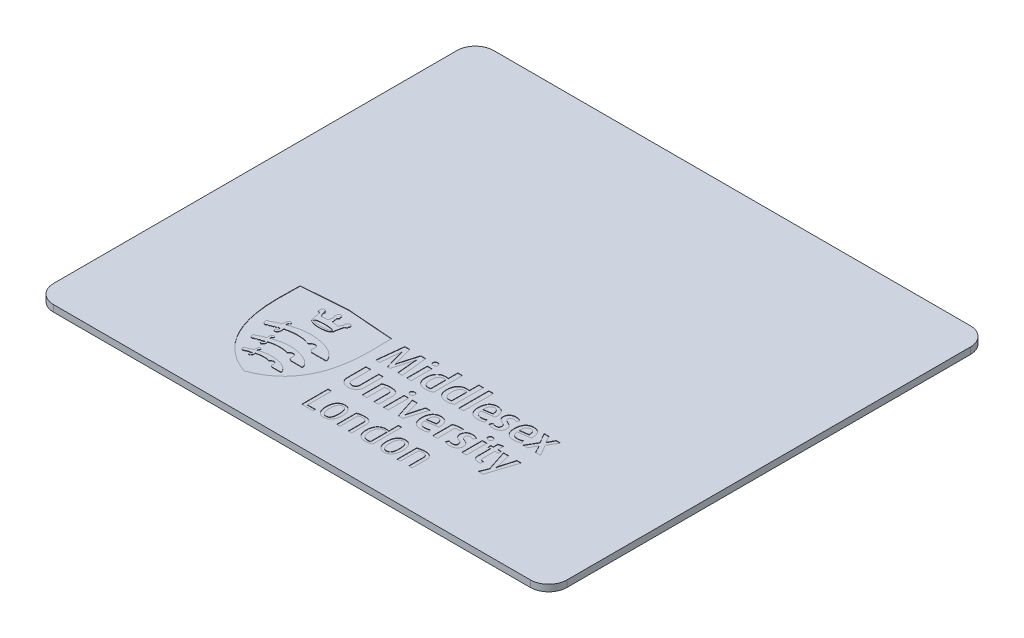
SolidWorks part; units mm, degrees
material "ABS"
ref_plane "Front Plane" through (0, 0, 0) normal (0, 0, 1) x (1, 0, 0)
ref_plane "Top Plane" through (0, 0, 0) normal (0, 1, 0) x (1, 0, 0)
ref_plane "Right Plane" through (0, 0, 0) normal (1, 0, 0) x (0, 0, -1)
sketch "Sketch1" plane through (0, 0, 0) normal (0, 1, 0) x (1, 0, 0)
  line L1 (-700, 600) -> (700, 600)
  line L2 (-700, 600) -> (-700, -600)
  line L3 (-700, -600) -> (700, -600)
  line L4 (700, 600) -> (700, -600)
  line L5 (0, -600) -> (0, 600) construction
  line L6 (-700, 0) -> (700, 0) construction
  point P0 (0, 0)
  dimension "D1" = 1400
  dimension "D2" = 1200
extrude "Boss-Extrude1" add sketch "Sketch1" along normal blind 18
sketch "Sketch2" plane through (0, 0, 0) normal (0, -1, 0) x (1, 0, 0)
  circle A0 centre (0, 0) radius 5
extrude "Cut-Extrude1" cut sketch "Sketch2" against normal blind 1
fillet "Fillet1" radius 50 4 edges at (700, 9, -600) (700, 9, 600) (-700, 9, 600) (-700, 9, -600)
sketch "Sketch3" plane through (0, 18, 0) normal (0, 1, 0) x (1, 0, 0)
  line L0 (-108.937, -219.6886) -> (-234.7326, -210.062)
  line L1 (-234.7326, -210.062) -> (-358.2136, -219.2576)
  line L2 (-24.6354, -235.7994) -> (-24.8453, -235.7994)
  line L3 (-40.5789, -291.8555) -> (-48.0791, -291.8555)
  line L4 (-63.7066, -235.7994) -> (-63.9144, -235.7994)
  line L5 (-68.808, -291.8555) -> (-79.9628, -291.8555)
  line L6 (-79.9628, -291.8555) -> (-71.9409, -220.1722)
  line L7 (-71.9409, -220.1722) -> (-58.6049, -220.1722)
  line L8 (-58.6049, -220.1722) -> (-45.7821, -266.1213)
  line L9 (-43.9096, -274.1443) -> (-43.7005, -274.1443)
  line L10 (-41.8247, -266.1213) -> (-28.5982, -220.1722)
  line L11 (-28.5982, -220.1722) -> (-15.2571, -220.1722)
  line L12 (-15.2571, -220.1722) -> (-7.2304, -291.8555)
  line L13 (-7.2304, -291.8555) -> (-19.7405, -291.8555)
  line L14 (4.7523, -235.6977) -> (17.4635, -235.6977)
  line L15 (17.4635, -235.6977) -> (17.4635, -291.8555)
  line L16 (17.4635, -291.8555) -> (4.7523, -291.8555)
  line L17 (4.7523, -291.8555) -> (4.7523, -235.6977)
  line L18 (62.3691, -283.5184) -> (62.3691, -243.0942)
  line L19 (62.3691, -236.2174) -> (62.3691, -210.0652)
  line L20 (62.3691, -210.0652) -> (75.0815, -210.0652)
  line L21 (75.0815, -210.0652) -> (75.0815, -288.8365)
  line L22 (119.5758, -283.5184) -> (119.5758, -243.0942)
  line L23 (119.5758, -236.2174) -> (119.5758, -210.0652)
  line L24 (119.5758, -210.0652) -> (132.2904, -210.0652)
  line L25 (132.2904, -210.0652) -> (132.2904, -288.8365)
  line L26 (146.9693, -210.0652) -> (159.6729, -210.0652)
  line L27 (159.6729, -210.0652) -> (159.6729, -291.8555)
  line L28 (159.6729, -291.8555) -> (146.9693, -291.8555)
  line L29 (146.9693, -291.8555) -> (146.9693, -210.0652)
  line L30 (183.0194, -261.9537) -> (206.2499, -258.4109)
  line L31 (213.2263, -280.9174) -> (216.2497, -288.9393)
  line L32 (218.1244, -263.4141) -> (183.7434, -268.415)
  line L33 (225.9145, -288.7294) -> (229.2617, -280.6033)
  line L34 (259.7856, -238.6117) -> (256.664, -246.0124)
  line L35 (281.883, -261.9537) -> (305.1112, -258.4109)
  line L36 (312.0987, -280.9174) -> (315.122, -288.9393)
  line L37 (316.988, -263.4141) -> (282.618, -268.415)
  line L38 (356.0547, -291.8555) -> (345.5278, -271.4349)
  line L39 (345.5278, -271.4349) -> (345.3244, -271.4349)
  line L40 (345.3244, -271.4349) -> (334.5832, -291.8555)
  line L41 (334.5832, -291.8555) -> (321.6674, -291.8555)
  line L42 (321.6674, -291.8555) -> (339.0722, -262.7895)
  line L43 (339.0722, -262.7895) -> (323.4394, -235.6977)
  line L44 (323.4394, -235.6977) -> (336.7839, -235.6977)
  line L45 (336.7839, -235.6977) -> (346.2608, -254.0335)
  line L46 (346.2608, -254.0335) -> (346.4664, -254.0335)
  line L47 (346.4664, -254.0335) -> (356.3632, -235.6977)
  line L48 (356.3632, -235.6977) -> (368.3383, -235.6977)
  line L49 (368.3383, -235.6977) -> (352.408, -261.9548)
  line L50 (352.408, -261.9548) -> (370.0119, -291.8555)
  line L51 (370.0119, -291.8555) -> (356.0547, -291.8555)
  line L52 (-77.3618, -371.7369) -> (-77.3618, -320.8951)
  line L53 (-77.3618, -320.8951) -> (-64.1232, -320.8951)
  line L54 (-64.1232, -320.8951) -> (-64.1232, -371.6363)
  line L55 (-42.3444, -371.6363) -> (-42.3444, -320.8951)
  line L56 (-42.3444, -320.8951) -> (-30.0518, -320.8951)
  line L57 (-30.0518, -320.8951) -> (-30.0518, -371.7369)
  line L58 (15.6893, -392.5764) -> (15.6893, -352.779)
  line L59 (-3.1681, -344.9679) -> (-3.1681, -392.5764)
  line L60 (-3.1681, -392.5764) -> (-15.8805, -392.5764)
  line L61 (-15.8805, -392.5764) -> (-15.8805, -339.4419)
  line L62 (28.4039, -352.5689) -> (28.4039, -392.5764)
  line L63 (28.4039, -392.5764) -> (15.6893, -392.5764)
  line L64 (42.3654, -336.4166) -> (55.0734, -336.4166)
  line L65 (55.0734, -336.4166) -> (55.0734, -392.572)
  line L66 (55.0734, -392.572) -> (42.3654, -392.572)
  line L67 (42.3654, -392.572) -> (42.3654, -336.4166)
  line L68 (94.8796, -392.5764) -> (82.7907, -392.5764)
  line L69 (82.7907, -392.5764) -> (64.454, -336.4197)
  line L70 (64.454, -336.4197) -> (77.9997, -336.4197)
  line L71 (77.9997, -336.4197) -> (87.8921, -372.6798)
  line L72 (89.253, -380.387) -> (89.4587, -380.387)
  line L73 (90.9199, -372.6798) -> (101.0203, -336.4197)
  line L74 (101.0203, -336.4197) -> (112.9013, -336.4197)
  line L75 (112.9013, -336.4197) -> (94.8796, -392.5764)
  line L76 (129.6629, -362.678) -> (152.8956, -359.1361)
  line L77 (159.8743, -381.6448) -> (162.9019, -389.6625)
  line L78 (164.7701, -364.1372) -> (130.3914, -369.1336)
  line L79 (189.0508, -345.1704) -> (189.0508, -392.5764)
  line L80 (189.0508, -392.5764) -> (176.3362, -392.5764)
  line L81 (176.3362, -392.5764) -> (176.3362, -339.441)
  line L82 (203.4345, -335.4791) -> (200.9273, -344.7569)
  line L83 (208.3216, -389.4568) -> (211.6511, -381.3276)
  line L84 (242.1817, -339.3391) -> (239.0643, -346.7378)
  line L85 (255.4214, -336.4166) -> (268.1337, -336.4166)
  line L86 (268.1337, -336.4166) -> (268.1337, -392.572)
  line L87 (268.1337, -392.572) -> (255.4214, -392.572)
  line L88 (255.4214, -392.572) -> (255.4214, -336.4166)
  line L89 (285.3221, -377.9893) -> (285.3221, -344.5467)
  line L90 (285.3221, -344.5467) -> (279.0784, -344.5467)
  line L91 (279.0784, -344.5467) -> (279.0784, -336.4166)
  line L92 (279.0784, -336.4166) -> (285.3221, -336.4166)
  line L93 (285.3221, -336.4166) -> (285.3221, -324.0181)
  line L94 (285.3221, -324.0181) -> (298.0432, -320.4785)
  line L95 (298.0432, -320.4785) -> (298.0432, -336.4166)
  line L96 (298.0432, -336.4166) -> (307.2026, -336.4166)
  line L97 (307.2026, -336.4166) -> (307.2026, -344.5467)
  line L98 (307.2026, -344.5467) -> (298.0432, -344.5467)
  line L99 (298.0432, -344.5467) -> (298.0432, -377.3679)
  line L100 (307.2026, -384.143) -> (307.2026, -392.0536)
  line L101 (336.0729, -414.9778) -> (322.63, -414.9778)
  line L102 (322.63, -414.9778) -> (331.796, -392.572)
  line L103 (331.796, -392.572) -> (313.2472, -336.4186)
  line L104 (313.2472, -336.4186) -> (326.8018, -336.4186)
  line L105 (326.8018, -336.4186) -> (336.4864, -372.7826)
  line L106 (337.6304, -380.809) -> (337.8406, -380.809)
  line L107 (339.3916, -372.7826) -> (349.8222, -336.4186)
  line L108 (349.8222, -336.4186) -> (361.7012, -336.4186)
  line L109 (361.7012, -336.4186) -> (336.0729, -414.9778)
  line L110 (-76.4178, -496.7756) -> (-76.4178, -425.0979)
  line L111 (-76.4178, -425.0979) -> (-66.8338, -425.0979)
  line L112 (-66.8338, -425.0979) -> (-66.8338, -490.3155)
  line L113 (-66.8338, -490.3155) -> (-45.2626, -490.3155)
  line L114 (-45.2626, -490.3155) -> (-45.2626, -496.7756)
  line L115 (-45.2626, -496.7756) -> (-76.4178, -496.7756)
  line L116 (50.2847, -496.7756) -> (50.2847, -456.4531)
  line L117 (27.8811, -447.497) -> (27.8811, -496.7756)
  line L118 (27.8811, -496.7756) -> (18.7149, -496.7756)
  line L119 (18.7149, -496.7756) -> (18.7149, -443.5286)
  line L120 (59.4574, -456.2497) -> (59.4574, -496.7756)
  line L121 (59.4574, -496.7756) -> (50.2847, -496.7756)
  line L122 (105.2927, -490.2149) -> (105.2927, -446.4491)
  line L123 (105.2927, -441.3431) -> (105.2927, -414.9821)
  line L124 (105.2927, -414.9821) -> (114.3605, -414.9821)
  line L125 (114.3605, -414.9821) -> (114.3605, -493.8661)
  line L126 (215.0113, -496.7756) -> (215.0113, -456.4531)
  line L127 (192.6099, -447.497) -> (192.6099, -496.7756)
  line L128 (192.6099, -496.7756) -> (183.4482, -496.7756)
  line L129 (183.4482, -496.7756) -> (183.4482, -443.5286)
  line L130 (224.1862, -456.2497) -> (224.1862, -496.7756)
  line L131 (224.1862, -496.7756) -> (215.0113, -496.7756)
  line L132 (-287.6033, -317.3665) -> (-287.8495, -317.476)
  line L133 (-283.8428, -360.4576) -> (-283.5695, -360.357)
  line L134 (-192.9487, -354.5454) -> (-186.1037, -360.9652)
  line L135 (-186.1037, -360.9652) -> (-145.5361, -360.9652)
  line L136 (-145.5361, -360.9652) -> (-145.5361, -360.2519)
  line L137 (-277.5347, -373.0626) -> (-277.7809, -373.1612)
  line L138 (-275.9499, -402.3069) -> (-275.9958, -402.3069)
  line L139 (-274.3748, -408.5417) -> (-274.1517, -408.4521)
  line L140 (-201.5593, -403.3986) -> (-195.3584, -408.8304)
  line L141 (-195.3584, -408.8304) -> (-162.7178, -408.8304)
  line L142 (-162.7178, -408.8304) -> (-162.7178, -408.1152)
  line L143 (-231.3232, -424.039) -> (-231.8711, -424.0345)
  line L144 (-264.1125, -430.4095) -> (-265.003, -430.72)
  line L145 (-266.9904, -420.6875) -> (-267.1687, -420.7664)
  line L146 (-264.2767, -450.8113) -> (-264.037, -450.715)
  line L147 (-210.0286, -445.6659) -> (-205.3461, -449.4549)
  line L148 (-205.3461, -449.4549) -> (-180.6346, -449.4549)
  line L149 (-180.6346, -449.4549) -> (-180.6346, -448.7417)
  line L150 (-204.3125, -247.2035) -> (-207.3172, -248.2963)
  line L151 (-207.3172, -248.2963) -> (-205.3165, -253.8025)
  line L152 (-230.9809, -246.1775) -> (-226.8288, -242.0398)
  line L153 (-226.8288, -242.0398) -> (-229.0962, -239.7799)
  line L154 (-239.3222, -239.7777) -> (-241.5767, -242.0342)
  line L155 (-241.5767, -242.0342) -> (-237.4244, -246.1896)
  line L156 (-262.6327, -253.7983) -> (-260.6331, -248.2963)
  line L157 (-260.6331, -248.2963) -> (-263.6412, -247.2035)
  line L158 (-272.9102, -251.5263) -> (-273.9951, -254.5279)
  line L159 (-273.9951, -254.5279) -> (-268.4474, -256.5492)
  line L160 (-199.528, -256.5579) -> (-193.9518, -254.5279)
  line L161 (-193.9518, -254.5279) -> (-195.0412, -251.5263)
  spline S0 degree 2 poles (-358.2136, -219.2576) (-359.0843, -246.2586) (-359.0843, -279.7218) knots 2 2 2 3 3 3
  spline S1 degree 2 poles (-359.0843, -279.7218) (-359.0843, -451.1395) (-233.9723, -496.7953) knots 3 3 3 4 4 4
  spline S2 degree 2 poles (-233.9723, -496.7953) (-108.0609, -451.5748) (-108.0609, -280.1549) knots 4 4 4 5 5 5
  spline S3 degree 2 poles (-108.0609, -280.1549) (-108.0609, -246.6939) (-108.937, -219.6886) knots 5 5 5 6 6 6
  spline S4 degree 2 poles (-19.7405, -291.8555) (-19.8402, -290.0867) (-24.3225, -244.4495) knots 0 0 0 1 1 1
  spline S5 degree 2 poles (-24.3225, -244.4495) (-24.7337, -239.9659) (-24.6354, -235.7994) knots 1 1 1 2 2 2
  spline S6 degree 2 poles (-24.8453, -235.7994) (-25.5716, -239.863) (-26.9226, -244.4495) knots 3 3 3 4 4 4
  spline S7 degree 2 poles (-26.9226, -244.4495) (-39.742, -289.4622) (-40.5789, -291.8555) knots 4 4 4 5 5 5
  spline S8 degree 2 poles (-48.0791, -291.8555) (-48.8043, -289.7729) (-61.6185, -244.3433) knots 6 6 6 7 7 7
  spline S9 degree 2 poles (-61.6185, -244.3433) (-62.8676, -239.863) (-63.7066, -235.7994) knots 7 7 7 8 8 8
  spline S10 degree 2 poles (-63.9144, -235.7994) (-63.8136, -239.863) (-64.226, -244.3433) knots 9 9 9 10 10 10
  spline S11 degree 2 poles (-64.226, -244.3433) (-68.7086, -289.7729) (-68.808, -291.8555) knots 10 10 10 11 11 11
  spline S12 degree 2 poles (-45.7821, -266.1213) (-44.5395, -270.7021) (-43.9096, -274.1443) knots 15 15 15 16 16 16
  spline S13 degree 2 poles (-43.7005, -274.1443) (-43.1788, -270.7021) (-41.8247, -266.1213) knots 17 17 17 18 18 18
  spline S14 degree 3 poles (11.1107, -213.4003) (15.0724, -213.4003) (18.0892, -216.2103) (18.0892, -219.7553) (18.0892, -223.1922) (15.0724, -226.0064) (11.1107, -226.0064) knots 2 2 2 2 3 3 3 4 4 4 4
  spline S15 degree 3 poles (11.1107, -226.0064) (7.2539, -226.0064) (4.1298, -223.1922) (4.1298, -219.7553) (4.1298, -216.2103) (7.2539, -213.4003) (11.1107, -213.4003) knots 0 0 0 0 1 1 1 2 2 2 2
  spline S16 degree 3 poles (62.3691, -243.0942) (60.5992, -242.5725) (58.7267, -242.3657) (56.7446, -242.3657) knots 0 0 0 0 1 1 1 1
  spline S17 degree 3 poles (56.7446, -242.3657) (45.6949, -242.3657) (41.9453, -251.8458) (41.9453, -263.7268) knots 1 1 1 1 2 2 2 2
  spline S18 degree 3 poles (41.9453, -263.7268) (41.9453, -276.4371) (46.0166, -284.772) (55.8127, -284.772) knots 2 2 2 2 3 3 3 3
  spline S19 degree 3 poles (55.8127, -284.772) (58.823, -284.772) (60.9144, -284.4602) (62.3691, -283.5184) knots 3 3 3 3 4 4 4 4
  spline S20 degree 3 poles (55.4935, -292.899) (38.9243, -292.899) (29.3423, -282.2713) (29.3423, -264.4542) knots 0 0 0 0 1 1 1 1
  spline S21 degree 3 poles (29.3423, -264.4542) (29.3423, -246.1175) (39.3443, -235.1749) (53.9357, -235.1749) knots 1 1 1 1 2 2 2 2
  spline S22 degree 3 poles (53.9357, -235.1749) (57.064, -235.1749) (59.8729, -235.4898) (62.3691, -236.2174) knots 2 2 2 2 3 3 3 3
  spline S23 degree 3 poles (75.0815, -288.8365) (70.6012, -291.3381) (64.2439, -292.899) (55.4935, -292.899) knots 6 6 6 6 7 7 7 7
  spline S24 degree 3 poles (119.5758, -243.0942) (117.8081, -242.5725) (115.9158, -242.3657) (113.947, -242.3657) knots 0 0 0 0 1 1 1 1
  spline S25 degree 3 poles (113.947, -242.3657) (102.9038, -242.3657) (99.1542, -251.8458) (99.1542, -263.7268) knots 1 1 1 1 2 2 2 2
  spline S26 degree 3 poles (99.1542, -263.7268) (99.1542, -276.4371) (103.208, -284.772) (113.0063, -284.772) knots 2 2 2 2 3 3 3 3
  spline S27 degree 3 poles (113.0063, -284.772) (116.0339, -284.772) (118.1078, -284.4602) (119.5758, -283.5184) knots 3 3 3 3 4 4 4 4
  spline S28 degree 3 poles (112.7044, -292.899) (96.1309, -292.899) (86.5447, -282.2713) (86.5447, -264.4542) knots 0 0 0 0 1 1 1 1
  spline S29 degree 3 poles (86.5447, -264.4542) (86.5447, -246.1175) (96.5465, -235.1749) (111.1316, -235.1749) knots 1 1 1 1 2 2 2 2
  spline S30 degree 3 poles (111.1316, -235.1749) (114.2577, -235.1749) (117.0753, -235.4898) (119.5758, -236.2174) knots 2 2 2 2 3 3 3 3
  spline S31 degree 3 poles (132.2904, -288.8365) (127.8078, -291.3381) (121.4528, -292.899) (112.7044, -292.899) knots 6 6 6 6 7 7 7 7
  spline S32 degree 3 poles (195.2002, -242.4663) (187.8104, -242.4663) (182.7045, -248.5129) (183.0194, -261.9537) knots 0 0 0 0 1 1 1 1
  spline S33 degree 3 poles (206.2499, -258.4109) (206.2499, -247.0548) (202.1831, -242.4663) (195.2002, -242.4663) knots 2 2 2 2 3 3 3 3
  spline S34 degree 3 poles (183.7434, -268.415) (184.7782, -278.8336) (189.7835, -284.039) (199.0548, -284.039) knots 0 0 0 0 1 1 1 1
  spline S35 degree 3 poles (199.0548, -284.039) (205.5172, -284.039) (210.2096, -282.4803) (213.2263, -280.9174) knots 1 1 1 1 2 2 2 2
  spline S36 degree 3 poles (216.2497, -288.9393) (212.29, -291.1271) (206.2499, -292.899) (197.7029, -292.899) knots 3 3 3 3 4 4 4 4
  spline S37 degree 3 poles (197.7029, -292.899) (181.7636, -292.899) (171.6525, -282.5843) (171.6525, -263.6208) knots 4 4 4 4 5 5 5 5
  spline S38 degree 3 poles (171.6525, -263.6208) (171.6525, -245.2828) (180.9303, -234.6531) (195.6312, -234.6531) knots 5 5 5 5 6 6 6 6
  spline S39 degree 3 poles (195.6312, -234.6531) (210.518, -234.6531) (218.6428, -244.5532) (218.1244, -263.4141) knots 6 6 6 6 7 7 7 7
  spline S40 degree 3 poles (241.4467, -292.7951) (234.8818, -292.7951) (229.2617, -291.0242) (225.9145, -288.7294) knots 0 0 0 0 1 1 1 1
  spline S41 degree 3 poles (229.2617, -280.6033) (231.3444, -282.2713) (235.1968, -283.8356) (239.7821, -283.8356) knots 2 2 2 2 3 3 3 3
  spline S42 degree 3 poles (239.7821, -283.8356) (244.9864, -283.8356) (248.4209, -280.4983) (248.4209, -275.9131) knots 3 3 3 3 4 4 4 4
  spline S43 degree 3 poles (248.4209, -275.9131) (248.4209, -271.121) (245.9227, -268.8296) (240.1911, -266.6441) knots 4 4 4 4 5 5 5 5
  spline S44 degree 3 poles (240.1911, -266.6441) (229.5679, -262.5794) (227.3825, -256.7472) (227.3825, -250.9105) knots 5 5 5 5 6 6 6 6
  spline S45 degree 3 poles (227.3825, -250.9105) (227.3825, -241.9479) (234.4595, -234.6531) (245.1963, -234.6531) knots 6 6 6 6 7 7 7 7
  spline S46 degree 3 poles (245.1963, -234.6531) (251.4442, -234.6531) (256.1259, -236.2174) (259.7856, -238.6117) knots 7 7 7 7 8 8 8 8
  spline S47 degree 3 poles (256.664, -246.0124) (254.9969, -244.6551) (251.6586, -242.8863) (247.699, -242.8863) knots 9 9 9 9 10 10 10 10
  spline S48 degree 3 poles (247.699, -242.8863) (242.4837, -242.8863) (239.6748, -246.3263) (239.6748, -250.2817) knots 10 10 10 10 11 11 11 11
  spline S49 degree 3 poles (239.6748, -250.2817) (239.6748, -254.8668) (243.1138, -257.1574) (248.0074, -259.1394) knots 11 11 11 11 12 12 12 12
  spline S50 degree 3 poles (248.0074, -259.1394) (258.9523, -263.5169) (261.4505, -269.1446) (261.4505, -275.7041) knots 12 12 12 12 13 13 13 13
  spline S51 degree 3 poles (261.4505, -275.7041) (261.4505, -284.8757) (253.7368, -292.7951) (241.4467, -292.7951) knots 13 13 13 13 14 14 14 14
  spline S52 degree 3 poles (294.0725, -242.4663) (286.6673, -242.4663) (281.5658, -248.5129) (281.883, -261.9537) knots 0 0 0 0 1 1 1 1
  spline S53 degree 3 poles (305.1112, -258.4109) (305.1112, -247.0548) (301.0532, -242.4663) (294.0725, -242.4663) knots 2 2 2 2 3 3 3 3
  spline S54 degree 3 poles (282.618, -268.415) (283.6572, -278.8336) (288.6559, -284.039) (297.9206, -284.039) knots 0 0 0 0 1 1 1 1
  spline S55 degree 3 poles (297.9206, -284.039) (304.3828, -284.039) (309.0709, -282.4803) (312.0987, -280.9174) knots 1 1 1 1 2 2 2 2
  spline S56 degree 3 poles (315.122, -288.9393) (311.1623, -291.1271) (305.1112, -292.899) (296.5707, -292.899) knots 3 3 3 3 4 4 4 4
  spline S57 degree 3 poles (296.5707, -292.899) (280.6317, -292.899) (270.5271, -282.5843) (270.5271, -263.6208) knots 4 4 4 4 5 5 5 5
  spline S58 degree 3 poles (270.5271, -263.6208) (270.5271, -245.2828) (279.7916, -234.6531) (294.4816, -234.6531) knots 5 5 5 5 6 6 6 6
  spline S59 degree 3 poles (294.4816, -234.6531) (309.3881, -234.6531) (317.5151, -244.5532) (316.988, -263.4141) knots 6 6 6 6 7 7 7 7
  spline S60 degree 3 poles (-53.7057, -393.725) (-67.769, -393.725) (-77.3618, -384.7599) (-77.3618, -371.7369) knots 0 0 0 0 1 1 1 1
  spline S61 degree 3 poles (-64.1232, -371.6363) (-64.1232, -379.3455) (-59.1158, -383.5108) (-53.1797, -383.5108) knots 4 4 4 4 5 5 5 5
  spline S62 degree 3 poles (-53.1797, -383.5108) (-47.1407, -383.5108) (-42.3444, -379.3455) (-42.3444, -371.6363) knots 5 5 5 5 6 6 6 6
  spline S63 degree 3 poles (-30.0518, -371.7369) (-30.0518, -384.7599) (-39.6372, -393.725) (-53.7057, -393.725) knots 9 9 9 9 10 10 10 10
  spline S64 degree 3 poles (15.6893, -352.779) (15.6893, -348.1948) (13.6024, -343.4027) (5.5868, -343.4027) knots 1 1 1 1 2 2 2 2
  spline S65 degree 3 poles (5.5868, -343.4027) (1.4161, -343.4027) (-0.7705, -344.023) (-3.1681, -344.9679) knots 2 2 2 2 3 3 3 3
  spline S66 degree 3 poles (-15.8805, -339.4419) (-10.5689, -336.9437) (-3.3792, -335.3839) (6.1065, -335.3839) knots 6 6 6 6 7 7 7 7
  spline S67 degree 3 poles (6.1065, -335.3839) (22.8802, -335.3839) (28.4039, -343.5044) (28.4039, -352.5689) knots 7 7 7 7 8 8 8 8
  spline S68 degree 3 poles (48.7227, -314.1212) (52.6888, -314.1212) (55.6989, -316.9377) (55.6989, -320.4785) (55.6989, -323.9187) (52.6888, -326.7307) (48.7227, -326.7307) knots 2 2 2 2 3 3 3 4 4 4 4
  spline S69 degree 3 poles (48.7227, -326.7307) (44.8723, -326.7307) (41.7374, -323.9187) (41.7374, -320.4785) (41.7374, -316.9377) (44.8723, -314.1212) (48.7227, -314.1212) knots 0 0 0 0 1 1 1 2 2 2 2
  spline S70 degree 2 poles (87.8921, -372.6798) (89.0451, -376.7445) (89.253, -380.387) knots 4 4 4 5 5 5
  spline S71 degree 2 poles (89.4587, -380.387) (89.7779, -376.8473) (90.9199, -372.6798) knots 6 6 6 7 7 7
  spline S72 degree 3 poles (141.8524, -343.1928) (134.4494, -343.1928) (129.3392, -349.236) (129.6629, -362.678) knots 0 0 0 0 1 1 1 1
  spline S73 degree 3 poles (152.8956, -359.1361) (152.8956, -347.7802) (148.8354, -343.1928) (141.8524, -343.1928) knots 2 2 2 2 3 3 3 3
  spline S74 degree 3 poles (130.3914, -369.1336) (131.4306, -379.5579) (136.4292, -384.7599) (145.6983, -384.7599) knots 0 0 0 0 1 1 1 1
  spline S75 degree 3 poles (145.6983, -384.7599) (152.1606, -384.7599) (156.8508, -383.2046) (159.8743, -381.6448) knots 1 1 1 1 2 2 2 2
  spline S76 degree 3 poles (162.9019, -389.6625) (158.9335, -391.8502) (152.8956, -393.6199) (144.3421, -393.6199) knots 3 3 3 3 4 4 4 4
  spline S77 degree 3 poles (144.3421, -393.6199) (128.4073, -393.6199) (118.3005, -383.3052) (118.3005, -364.3429) knots 4 4 4 4 5 5 5 5
  spline S78 degree 3 poles (118.3005, -364.3429) (118.3005, -346.0028) (127.5672, -335.3817) (142.2594, -335.3817) knots 5 5 5 5 6 6 6 6
  spline S79 degree 3 poles (142.2594, -335.3817) (157.1615, -335.3817) (165.2952, -345.2786) (164.7701, -364.1372) knots 6 6 6 6 7 7 7 7
  spline S80 degree 3 poles (200.9273, -344.7569) (196.6572, -343.301) (191.9712, -343.5044) (189.0508, -345.1704) knots 0 0 0 0 1 1 1 1
  spline S81 degree 3 poles (176.3362, -339.441) (182.1662, -336.6276) (189.2564, -335.0624) (203.4345, -335.4791) knots 4 4 4 4 5 5 5 5
  spline S82 degree 3 poles (223.8451, -393.5171) (217.2844, -393.5171) (211.6511, -391.7364) (208.3216, -389.4568) knots 0 0 0 0 1 1 1 1
  spline S83 degree 3 poles (211.6511, -381.3276) (213.7382, -382.999) (217.6016, -384.5565) (222.1824, -384.5565) knots 2 2 2 2 3 3 3 3
  spline S84 degree 3 poles (222.1824, -384.5565) (227.389, -384.5565) (230.8323, -381.2248) (230.8323, -376.6372) knots 3 3 3 3 4 4 4 4
  spline S85 degree 3 poles (230.8323, -376.6372) (230.8323, -371.8464) (228.3276, -369.5536) (222.6002, -367.3617) knots 4 4 4 4 5 5 5 5
  spline S86 degree 3 poles (222.6002, -367.3617) (211.9705, -363.3014) (209.783, -357.4726) (209.783, -351.6337) knots 5 5 5 5 6 6 6 6
  spline S87 degree 3 poles (209.783, -351.6337) (209.783, -342.6666) (216.8708, -335.3839) (227.6013, -335.3839) knots 6 6 6 6 7 7 7 7
  spline S88 degree 3 poles (227.6013, -335.3839) (233.8535, -335.3839) (238.5372, -336.9415) (242.1817, -339.3391) knots 7 7 7 7 8 8 8 8
  spline S89 degree 3 poles (239.0643, -346.7378) (237.4062, -345.3792) (234.0634, -343.6117) (230.0995, -343.6117) knots 9 9 9 9 10 10 10 10
  spline S90 degree 3 poles (230.0995, -343.6117) (224.8885, -343.6117) (222.0861, -347.0483) (222.0861, -351.0057) knots 10 10 10 10 11 11 11 11
  spline S91 degree 3 poles (222.0861, -351.0057) (222.0861, -355.5922) (225.5164, -357.8827) (230.4167, -359.8581) knots 11 11 11 11 12 12 12 12
  spline S92 degree 3 poles (230.4167, -359.8581) (241.3527, -364.242) (243.8531, -369.8731) (243.8531, -376.4315) knots 12 12 12 12 13 13 13 13
  spline S93 degree 3 poles (243.8531, -376.4315) (243.8531, -385.5977) (236.1418, -393.5171) (223.8451, -393.5171) knots 13 13 13 13 14 14 14 14
  spline S94 degree 3 poles (261.7829, -314.1212) (265.7361, -314.1212) (268.7616, -316.9377) (268.7616, -320.4785) (268.7616, -323.9187) (265.7361, -326.7307) (261.7829, -326.7307) knots 2 2 2 2 3 3 3 4 4 4 4
  spline S95 degree 3 poles (261.7829, -326.7307) (257.9241, -326.7307) (254.7957, -323.9187) (254.7957, -320.4785) (254.7957, -316.9377) (257.9241, -314.1212) (261.7829, -314.1212) knots 0 0 0 0 1 1 1 2 2 2 2
  spline S96 degree 3 poles (300.7492, -393.2021) (289.6973, -393.2021) (285.3221, -385.8079) (285.3221, -377.9893) knots 0 0 0 0 1 1 1 1
  spline S97 degree 3 poles (298.0432, -377.3679) (298.0432, -381.7476) (299.8086, -384.6593) (304.1838, -384.6593) knots 12 12 12 12 13 13 13 13
  spline S98 degree 3 poles (304.1838, -384.6593) (305.3301, -384.6593) (306.1679, -384.4515) (307.2026, -384.143) knots 13 13 13 13 14 14 14 14
  spline S99 degree 3 poles (307.2026, -392.0536) (306.0564, -392.5764) (303.7638, -393.2021) (300.7492, -393.2021) knots 15 15 15 15 16 16 16 16
  spline S100 degree 2 poles (336.4864, -372.7826) (337.6304, -377.1623) (337.6304, -380.809) knots 5 5 5 6 6 6
  spline S101 degree 2 poles (337.8406, -380.809) (338.1578, -377.1623) (339.3916, -372.7826) knots 7 7 7 8 8 8
  spline S102 degree 3 poles (-15.7765, -491.4663) (-5.0429, -491.4663) (-3.0676, -480.003) (-3.0676, -468.7477) (-3.0676, -457.4966) (-5.0429, -445.4079) (-15.7765, -445.4079) knots 2 2 2 2 3 3 3 4 4 4 4
  spline S103 degree 3 poles (-15.7765, -445.4079) (-26.5079, -445.4079) (-28.596, -457.3917) (-28.596, -468.7477) (-28.596, -480.1126) (-26.3056, -491.4663) (-15.7765, -491.4663) knots 0 0 0 0 1 1 1 2 2 2 2
  spline S104 degree 3 poles (-15.8805, -439.5777) (-0.4632, -439.5777) (6.1065, -451.9751) (6.1065, -468.7477) (6.1065, -485.214) (-0.566, -497.8258) (-15.7765, -497.8258) knots 2 2 2 2 3 3 3 4 4 4 4
  spline S105 degree 3 poles (-15.7765, -497.8258) (-31.0986, -497.8258) (-37.7633, -485.214) (-37.7633, -468.7477) (-37.7633, -451.9751) (-30.9871, -439.5777) (-15.8805, -439.5777) knots 0 0 0 0 1 1 1 2 2 2 2
  spline S106 degree 3 poles (50.2847, -456.4531) (50.2847, -451.2443) (48.0992, -445.515) (38.5085, -445.515) knots 1 1 1 1 2 2 2 2
  spline S107 degree 3 poles (38.5085, -445.515) (33.3065, -445.515) (30.8015, -446.2457) (27.8811, -447.497) knots 2 2 2 2 3 3 3 3
  spline S108 degree 3 poles (18.7149, -443.5286) (23.718, -441.1375) (30.2787, -439.5777) (39.2435, -439.5777) knots 6 6 6 6 7 7 7 7
  spline S109 degree 3 poles (39.2435, -439.5777) (54.8589, -439.5777) (59.4574, -448.2255) (59.4574, -456.2497) knots 7 7 7 7 8 8 8 8
  spline S110 degree 3 poles (105.2927, -446.4491) (103.0044, -445.8279) (100.7118, -445.4079) (98.3097, -445.4079) knots 0 0 0 0 1 1 1 1
  spline S111 degree 3 poles (98.3097, -445.4079) (85.2934, -445.4079) (81.1258, -456.6565) (81.1258, -468.8505) knots 1 1 1 1 2 2 2 2
  spline S112 degree 3 poles (81.1258, -468.8505) (81.1258, -482.0857) (85.7069, -491.7747) (97.1679, -491.7747) knots 2 2 2 2 3 3 3 3
  spline S113 degree 3 poles (97.1679, -491.7747) (100.9217, -491.7747) (103.5207, -491.3612) (105.2927, -490.2149) knots 3 3 3 3 4 4 4 4
  spline S114 degree 3 poles (96.7479, -497.8258) (80.7125, -497.8258) (72.0582, -486.5682) (72.0582, -469.5812) knots 0 0 0 0 1 1 1 1
  spline S115 degree 3 poles (72.0582, -469.5812) (72.0582, -450.9339) (81.9551, -440.0918) (96.4349, -440.0918) knots 1 1 1 1 2 2 2 2
  spline S116 degree 3 poles (96.4349, -440.0918) (99.5588, -440.0918) (102.2738, -440.5163) (105.2927, -441.3431) knots 2 2 2 2 3 3 3 3
  spline S117 degree 3 poles (114.3605, -493.8661) (110.6087, -496.1544) (104.5664, -497.8258) (96.7479, -497.8258) knots 6 6 6 6 7 7 7 7
  spline S118 degree 3 poles (148.9536, -491.4663) (159.6949, -491.4663) (161.6702, -480.003) (161.6702, -468.7477) (161.6702, -457.4966) (159.6949, -445.4079) (148.9536, -445.4079) knots 2 2 2 2 3 3 3 4 4 4 4
  spline S119 degree 3 poles (148.9536, -445.4079) (138.2296, -445.4079) (136.134, -457.3917) (136.134, -468.7477) (136.134, -480.1126) (138.4333, -491.4663) (148.9536, -491.4663) knots 0 0 0 0 1 1 1 2 2 2 2
  spline S120 degree 3 poles (148.8486, -439.5777) (164.267, -439.5777) (170.8387, -451.9751) (170.8387, -468.7477) (170.8387, -485.214) (164.1707, -497.8258) (148.9536, -497.8258) knots 2 2 2 2 3 3 3 4 4 4 4
  spline S121 degree 3 poles (148.9536, -497.8258) (133.6378, -497.8258) (126.9765, -485.214) (126.9765, -468.7477) (126.9765, -451.9751) (133.7494, -439.5777) (148.8486, -439.5777) knots 0 0 0 0 1 1 1 2 2 2 2
  spline S122 degree 3 poles (215.0113, -456.4531) (215.0113, -451.2443) (212.8281, -445.515) (203.2463, -445.515) knots 1 1 1 1 2 2 2 2
  spline S123 degree 3 poles (203.2463, -445.515) (198.031, -445.515) (195.5284, -446.2457) (192.6099, -447.497) knots 2 2 2 2 3 3 3 3
  spline S124 degree 3 poles (183.4482, -443.5286) (188.4491, -441.1375) (195.0033, -439.5777) (203.9681, -439.5777) knots 6 6 6 6 7 7 7 7
  spline S125 degree 3 poles (203.9681, -439.5777) (219.5966, -439.5777) (224.1862, -448.2255) (224.1862, -456.2497) knots 7 7 7 7 8 8 8 8
  spline S126 degree 3 poles (-229.5523, -319.5531) (-254.0144, -319.5531) (-276.1806, -327.4932) (-285.2594, -331.2363) knots 0 0 0 0 1 1 1 1
  spline S127 degree 3 poles (-285.2594, -331.2363) (-286.2547, -328.0893) (-285.9397, -326.0067) (-285.3885, -324.7159) knots 1 1 1 1 2 2 2 2
  spline S128 degree 3 poles (-285.3885, -324.7159) (-283.3013, -324.5398) (-281.653, -322.8544) (-281.653, -320.81) knots 2 2 2 2 3 3 3 3
  spline S129 degree 3 poles (-281.653, -320.81) (-281.653, -318.6496) (-283.4906, -316.8951) (-285.7516, -316.8951) knots 3 3 3 3 4 4 4 4
  spline S130 degree 3 poles (-285.7516, -316.8951) (-285.9516, -316.8951) (-286.1113, -316.9388) (-286.3159, -316.9935) knots 4 4 4 4 5 5 5 5
  spline S131 degree 3 poles (-286.3159, -316.9935) (-286.5435, -317.0188) (-286.7502, -317.0602) (-286.981, -317.1248) knots 5 5 5 5 6 6 6 6
  spline S132 degree 3 poles (-286.981, -317.1248) (-287.2063, -317.1884) (-287.4086, -317.2726) (-287.6033, -317.3665) knots 6 6 6 6 7 7 7 7
  spline S133 degree 3 poles (-287.8495, -317.476) (-287.8988, -317.511) (-288.0889, -317.6335) (-288.2979, -317.8062) knots 8 8 8 8 9 9 9 9
  spline S134 degree 3 poles (-288.2979, -317.8062) (-288.463, -317.9343) (-288.6098, -318.0513) (-288.7321, -318.1693) knots 9 9 9 9 10 10 10 10
  spline S135 degree 3 poles (-288.7321, -318.1693) (-290.0645, -319.377) (-294.1346, -323.8967) (-291.7621, -332.4175) knots 10 10 10 10 11 11 11 11
  spline S136 degree 3 poles (-291.7621, -332.4175) (-293.1534, -332.9908) (-294.1673, -334.243) (-294.6552, -335.9397) knots 11 11 11 11 12 12 12 12
  spline S137 degree 3 poles (-294.6552, -335.9397) (-295.9984, -335.2636) (-297.4117, -335.1379) (-298.6335, -335.6126) knots 12 12 12 12 13 13 13 13
  spline S138 degree 3 poles (-298.6335, -335.6126) (-300.0795, -336.1682) (-301.1393, -337.495) (-301.5923, -339.2549) knots 13 13 13 13 14 14 14 14
  spline S139 degree 3 poles (-301.5923, -339.2549) (-302.9431, -338.5167) (-304.3683, -338.3689) (-305.6044, -338.8339) knots 14 14 14 14 15 15 15 15
  spline S140 degree 3 poles (-305.6044, -338.8339) (-307.0799, -339.4059) (-308.1169, -340.7645) (-308.5127, -342.5671) knots 15 15 15 15 16 16 16 16
  spline S141 degree 3 poles (-308.5127, -342.5671) (-309.8582, -341.7663) (-311.3391, -341.586) (-312.5752, -342.0694) knots 16 16 16 16 17 17 17 17
  spline S142 degree 3 poles (-312.5752, -342.0694) (-314.0508, -342.6415) (-315.0714, -344.0591) (-315.4137, -345.9164) knots 17 17 17 17 18 18 18 18
  spline S143 degree 3 poles (-315.4137, -345.9164) (-316.747, -345.0346) (-318.2358, -344.7974) (-319.5472, -345.2929) knots 18 18 18 18 19 19 19 19
  spline S144 degree 3 poles (-319.5472, -345.2929) (-322.1319, -346.3023) (-323.1502, -349.9656) (-321.8048, -353.456) knots 19 19 19 19 20 20 20 20
  spline S145 degree 3 poles (-321.8048, -353.456) (-320.465, -356.9146) (-317.26, -358.9874) (-314.625, -357.9681) knots 20 20 20 20 21 21 21 21
  spline S146 degree 3 poles (-314.625, -357.9681) (-313.2786, -357.4385) (-312.3225, -356.1643) (-311.9518, -354.5006) knots 21 21 21 21 22 22 22 22
  spline S147 degree 3 poles (-311.9518, -354.5006) (-310.5123, -355.5212) (-308.8584, -355.8252) (-307.4518, -355.2815) knots 22 22 22 22 23 23 23 23
  spline S148 degree 3 poles (-307.4518, -355.2815) (-306.1185, -354.7598) (-305.1438, -353.5534) (-304.7161, -351.9486) knots 23 23 23 23 24 24 24 24
  spline S149 degree 3 poles (-304.7161, -351.9486) (-303.2778, -352.8839) (-301.6599, -353.1278) (-300.2852, -352.5951) knots 24 24 24 24 25 25 25 25
  spline S150 degree 3 poles (-300.2852, -352.5951) (-298.9561, -352.0844) (-297.9794, -350.9184) (-297.5067, -349.3346) knots 25 25 25 25 26 26 26 26
  spline S151 degree 3 poles (-297.5067, -349.3346) (-296.0443, -350.2237) (-294.4473, -350.4271) (-293.1064, -349.9087) knots 26 26 26 26 27 27 27 27
  spline S152 degree 3 poles (-293.1064, -349.9087) (-291.8004, -349.4034) (-290.8136, -348.2723) (-290.2986, -346.7367) knots 27 27 27 27 28 28 28 28
  spline S153 degree 3 poles (-290.2986, -346.7367) (-288.8318, -347.557) (-287.2686, -347.7387) (-285.9288, -347.2201) knots 28 28 28 28 29 29 29 29
  spline S154 degree 3 poles (-285.9288, -347.2201) (-285.6891, -347.126) (-285.4595, -347.008) (-285.231, -346.8624) knots 29 29 29 29 30 30 30 30
  spline S155 degree 3 poles (-285.231, -346.8624) (-284.3766, -350.0651) (-284.9924, -352.0635) (-285.6127, -353.1442) knots 30 30 30 30 31 31 31 31
  spline S156 degree 3 poles (-285.6127, -353.1442) (-285.6553, -353.1377) (-285.6989, -353.1343) (-285.7516, -353.1343) knots 31 31 31 31 32 32 32 32
  spline S157 degree 3 poles (-285.7516, -353.1343) (-288.0047, -353.1343) (-289.8425, -354.8899) (-289.8425, -357.0525) knots 32 32 32 32 33 33 33 33
  spline S158 degree 3 poles (-289.8425, -357.0525) (-289.8425, -359.8232) (-286.819, -362.0041) (-283.8428, -360.4576) knots 33 33 33 33 34 34 34 34
  spline S159 degree 3 poles (-283.5695, -360.357) (-283.1821, -360.1339) (-279.7563, -358.0357) (-278.5565, -353.1343) knots 35 35 35 35 36 36 36 36
  spline S160 degree 3 poles (-278.5565, -353.1343) (-277.8477, -350.2468) (-278.1004, -347.0266) (-279.298, -343.5602) knots 36 36 36 36 37 37 37 37
  spline S161 degree 3 poles (-279.298, -343.5602) (-267.8885, -340.4603) (-256.4526, -338.8852) (-245.2945, -338.8852) knots 37 37 37 37 38 38 38 38
  spline S162 degree 3 poles (-245.2945, -338.8852) (-225.702, -338.8852) (-212.7873, -343.7703) (-209.9894, -344.9296) knots 38 38 38 38 39 39 39 39
  spline S163 degree 3 poles (-209.9894, -344.9296) (-206.3098, -338.9827) (-200.0685, -336.0817) (-195.5325, -338.4773) knots 39 39 39 39 40 40 40 40
  spline S164 degree 3 poles (-195.5325, -338.4773) (-190.8891, -340.933) (-189.8226, -348.0176) (-192.9487, -354.5454) knots 40 40 40 40 41 41 41 41
  spline S165 degree 3 poles (-145.5361, -360.2519) (-145.5361, -353.9372) (-160.1387, -321.4729) (-229.5523, -319.5531) knots 44 44 44 44 45 45 45 45
  spline S166 degree 3 poles (-230.062, -375.4143) (-230.4634, -375.4035) (-230.8617, -375.3991) (-231.2631, -375.3991) knots 0 0 0 0 1 1 1 1
  spline S167 degree 3 poles (-231.2631, -375.3991) (-247.0621, -375.3991) (-266.8997, -381.7476) (-275.3746, -384.7382) knots 1 1 1 1 2 2 2 2
  spline S168 degree 3 poles (-275.3746, -384.7382) (-276.2594, -382.126) (-276.0482, -380.3957) (-275.6141, -379.3193) knots 2 2 2 2 3 3 3 3
  spline S169 degree 3 poles (-275.6141, -379.3193) (-273.8782, -379.1356) (-272.5218, -377.7181) (-272.5218, -376.005) knots 3 3 3 3 4 4 4 4
  spline S170 degree 3 poles (-272.5218, -376.005) (-272.5218, -374.1697) (-274.0793, -372.6733) (-275.9958, -372.6733) knots 4 4 4 4 5 5 5 5
  spline S171 degree 3 poles (-275.9958, -372.6733) (-276.173, -372.6733) (-276.324, -372.7169) (-276.477, -372.7564) knots 5 5 5 5 6 6 6 6
  spline S172 degree 3 poles (-276.477, -372.7564) (-276.6696, -372.7696) (-276.8533, -372.8068) (-277.0491, -372.8637) knots 6 6 6 6 7 7 7 7
  spline S173 degree 3 poles (-277.0491, -372.8637) (-277.2438, -372.9313) (-277.4254, -372.9949) (-277.5347, -373.0626) knots 7 7 7 7 8 8 8 8
  spline S174 degree 3 poles (-277.7809, -373.1612) (-277.8125, -373.1851) (-277.9658, -373.2902) (-278.1824, -373.4609) knots 9 9 9 9 10 10 10 10
  spline S175 degree 3 poles (-278.1824, -373.4609) (-278.3168, -373.566) (-278.446, -373.6708) (-278.5106, -373.7496) knots 10 10 10 10 11 11 11 11
  spline S176 degree 3 poles (-278.5106, -373.7496) (-280.0036, -375.0796) (-283.1176, -378.8928) (-280.9223, -386.0135) knots 11 11 11 11 12 12 12 12
  spline S177 degree 3 poles (-280.9223, -386.0135) (-281.0688, -386.0442) (-281.2023, -386.0856) (-281.3358, -386.136) knots 12 12 12 12 13 13 13 13
  spline S178 degree 3 poles (-281.3358, -386.136) (-282.5238, -386.6042) (-283.4129, -387.6412) (-283.8526, -389.05) knots 13 13 13 13 14 14 14 14
  spline S179 degree 3 poles (-283.8526, -389.05) (-284.9749, -388.5249) (-286.1553, -388.4461) (-287.1582, -388.8399) knots 14 14 14 14 15 15 15 15
  spline S180 degree 3 poles (-287.1582, -388.8399) (-288.3613, -389.3081) (-289.2518, -390.38) (-289.6586, -391.8195) knots 15 15 15 15 16 16 16 16
  spline S181 degree 3 poles (-289.6586, -391.8195) (-290.7634, -391.253) (-291.9579, -391.1457) (-292.9729, -391.5372) knots 16 16 16 16 17 17 17 17
  spline S182 degree 3 poles (-292.9729, -391.5372) (-294.2023, -392.0054) (-295.0753, -393.108) (-295.4471, -394.5847) knots 17 17 17 17 18 18 18 18
  spline S183 degree 3 poles (-295.4471, -394.5847) (-296.5573, -393.9698) (-297.7574, -393.8408) (-298.8062, -394.2391) knots 18 18 18 18 19 19 19 19
  spline S184 degree 3 poles (-298.8062, -394.2391) (-300.0291, -394.7093) (-300.8835, -395.8665) (-301.1973, -397.3892) knots 19 19 19 19 20 20 20 20
  spline S185 degree 3 poles (-301.1973, -397.3892) (-302.3163, -396.6956) (-303.5741, -396.5142) (-304.6319, -396.9429) knots 20 20 20 20 21 21 21 21
  spline S186 degree 3 poles (-304.6319, -396.9429) (-305.5213, -397.2841) (-306.2179, -397.9799) (-306.6523, -398.949) knots 21 21 21 21 22 22 22 22
  spline S187 degree 3 poles (-306.6523, -398.949) (-307.2878, -400.373) (-307.2571, -402.1889) (-306.5887, -403.9171) knots 22 22 22 22 23 23 23 23
  spline S188 degree 3 poles (-306.5887, -403.9171) (-305.4435, -406.8661) (-302.6718, -408.6205) (-300.448, -407.763) knots 23 23 23 23 24 24 24 24
  spline S189 degree 3 poles (-300.448, -407.763) (-299.3214, -407.3168) (-298.5273, -406.2886) (-298.1991, -404.9102) knots 24 24 24 24 25 25 25 25
  spline S190 degree 3 poles (-298.1991, -404.9102) (-296.9926, -405.7218) (-295.6145, -405.9516) (-294.442, -405.5054) knots 25 25 25 25 26 26 26 26
  spline S191 degree 3 poles (-294.442, -405.5054) (-293.3416, -405.0744) (-292.5506, -404.0943) (-292.1799, -402.7599) knots 26 26 26 26 27 27 27 27
  spline S192 degree 3 poles (-292.1799, -402.7599) (-290.9603, -403.5233) (-289.5907, -403.705) (-288.4456, -403.2608) knots 27 27 27 27 28 28 28 28
  spline S193 degree 3 poles (-288.4456, -403.2608) (-287.3376, -402.8298) (-286.5173, -401.8869) (-286.1026, -400.6006) knots 28 28 28 28 29 29 29 29
  spline S194 degree 3 poles (-286.1026, -400.6006) (-284.8873, -401.3007) (-283.5695, -401.4494) (-282.446, -401.0119) knots 29 29 29 29 30 30 30 30
  spline S195 degree 3 poles (-282.446, -401.0119) (-281.3566, -400.5919) (-280.5265, -399.673) (-280.08, -398.4174) knots 30 30 30 30 31 31 31 31
  spline S196 degree 3 poles (-280.08, -398.4174) (-278.8582, -399.0693) (-277.561, -399.1963) (-276.442, -398.763) knots 31 31 31 31 32 32 32 32
  spline S197 degree 3 poles (-276.442, -398.763) (-276.0997, -398.6275) (-275.7814, -398.4481) (-275.485, -398.214) knots 32 32 32 32 33 33 33 33
  spline S198 degree 3 poles (-275.485, -398.214) (-275.1338, -400.1544) (-275.4817, -401.4604) (-275.9499, -402.3069) knots 33 33 33 33 34 34 34 34
  spline S199 degree 3 poles (-275.9958, -402.3069) (-277.9153, -402.3069) (-279.4763, -403.8011) (-279.4763, -405.6409) knots 35 35 35 35 36 36 36 36
  spline S200 degree 3 poles (-279.4763, -405.6409) (-279.4763, -407.483) (-277.9153, -408.9749) (-275.9958, -408.9749) knots 36 36 36 36 37 37 37 37
  spline S201 degree 3 poles (-275.9958, -408.9749) (-275.4588, -408.9749) (-274.9337, -408.8304) (-274.3748, -408.5417) knots 37 37 37 37 38 38 38 38
  spline S202 degree 3 poles (-274.1517, -408.4521) (-273.8334, -408.2684) (-270.9828, -406.5314) (-269.9886, -402.4644) knots 39 39 39 39 40 40 40 40
  spline S203 degree 3 poles (-269.9886, -402.4644) (-269.4241, -400.1784) (-269.5303, -398.0717) (-270.3385, -395.5296) knots 40 40 40 40 41 41 41 41
  spline S204 degree 3 poles (-270.3385, -395.5296) (-260.3486, -392.7339) (-250.6311, -391.3164) (-241.4475, -391.3164) knots 41 41 41 41 42 42 42 42
  spline S205 degree 3 poles (-241.4475, -391.3164) (-228.7604, -391.3164) (-220.7284, -394.0422) (-218.1285, -395.0659) knots 42 42 42 42 43 43 43 43
  spline S206 degree 3 poles (-218.1285, -395.0659) (-214.5954, -389.6121) (-208.7829, -386.9936) (-204.5421, -389.238) knots 43 43 43 43 44 44 44 44
  spline S207 degree 3 poles (-204.5421, -389.238) (-200.3846, -391.4322) (-199.2338, -397.5162) (-201.5593, -403.3986) knots 44 44 44 44 45 45 45 45
  spline S208 degree 3 poles (-162.7178, -408.1152) (-162.7178, -403.0509) (-174.4205, -376.9479) (-230.062, -375.4143) knots 48 48 48 48 49 49 49 49
  spline S209 degree 3 poles (-231.8711, -424.0345) (-246.0021, -424.0345) (-256.4678, -427.7186) (-264.1125, -430.4095) knots 1 1 1 1 2 2 2 2
  spline S210 degree 3 poles (-265.003, -430.72) (-265.9743, -428.1539) (-265.6833, -427.0383) (-265.2655, -426.1808) knots 3 3 3 3 4 4 4 4
  spline S211 degree 3 poles (-265.2655, -426.1808) (-263.7756, -425.9904) (-262.6195, -424.761) (-262.6195, -423.282) knots 4 4 4 4 5 5 5 5
  spline S212 degree 3 poles (-262.6195, -423.282) (-262.6195, -421.672) (-263.9877, -420.3551) (-265.6669, -420.3551) knots 5 5 5 5 6 6 6 6
  spline S213 degree 3 poles (-265.6669, -420.3551) (-265.8363, -420.3551) (-265.9698, -420.3943) (-266.0596, -420.4294) knots 6 6 6 6 7 7 7 7
  spline S214 degree 3 poles (-266.0596, -420.4294) (-266.2247, -420.4404) (-266.3975, -420.4731) (-266.5955, -420.5278) knots 7 7 7 7 8 8 8 8
  spline S215 degree 3 poles (-266.5955, -420.5278) (-266.7541, -420.5892) (-266.9084, -420.6393) (-266.9904, -420.6875) knots 8 8 8 8 9 9 9 9
  spline S216 degree 3 poles (-267.1687, -420.7664) (-267.2147, -420.7881) (-267.3535, -420.8799) (-267.5536, -421.0332) knots 10 10 10 10 11 11 11 11
  spline S217 degree 3 poles (-267.5536, -421.0332) (-267.6761, -421.1295) (-267.7866, -421.2256) (-267.8677, -421.3022) knots 11 11 11 11 12 12 12 12
  spline S218 degree 3 poles (-267.8677, -421.3022) (-268.839, -422.1707) (-271.7693, -425.4303) (-269.9492, -431.582) knots 12 12 12 12 13 13 13 13
  spline S219 degree 3 poles (-269.9492, -431.582) (-269.972, -431.582) (-269.9886, -431.595) (-270.005, -431.5994) knots 13 13 13 13 14 14 14 14
  spline S220 degree 3 poles (-270.005, -431.5994) (-270.9422, -431.9648) (-271.6392, -432.7677) (-272.0133, -433.8833) knots 14 14 14 14 15 15 15 15
  spline S221 degree 3 poles (-272.0133, -433.8833) (-272.908, -433.4787) (-273.8202, -433.4328) (-274.6208, -433.7433) knots 15 15 15 15 16 16 16 16
  spline S222 degree 3 poles (-274.6208, -433.7433) (-275.5757, -434.1109) (-276.2724, -434.9444) (-276.6138, -436.0842) knots 16 16 16 16 17 17 17 17
  spline S223 degree 3 poles (-276.6138, -436.0842) (-277.502, -435.64) (-278.446, -435.5656) (-279.2422, -435.8828) knots 17 17 17 17 18 18 18 18
  spline S224 degree 3 poles (-279.2422, -435.8828) (-280.2093, -436.2569) (-280.9006, -437.1209) (-281.211, -438.2782) knots 18 18 18 18 19 19 19 19
  spline S225 degree 3 poles (-281.211, -438.2782) (-282.1102, -437.8035) (-283.0433, -437.7094) (-283.869, -438.0266) knots 19 19 19 19 20 20 20 20
  spline S226 degree 3 poles (-283.869, -438.0266) (-284.8414, -438.403) (-285.5327, -439.2954) (-285.8161, -440.4704) knots 20 20 20 20 21 21 21 21
  spline S227 degree 3 poles (-285.8161, -440.4704) (-286.7119, -439.9518) (-287.6613, -439.8512) (-288.4861, -440.1684) knots 21 21 21 21 22 22 22 22
  spline S228 degree 3 poles (-288.4861, -440.1684) (-289.2276, -440.4507) (-289.8085, -441.0282) (-290.1716, -441.842) knots 22 22 22 22 23 23 23 23
  spline S229 degree 3 poles (-290.1716, -441.842) (-290.6868, -443.0058) (-290.6671, -444.4825) (-290.1225, -445.8891) knots 23 23 23 23 24 24 24 24
  spline S230 degree 3 poles (-290.1225, -445.8891) (-289.1884, -448.3042) (-286.9012, -449.7394) (-285.0527, -449.0174) knots 24 24 24 24 25 25 25 25
  spline S231 degree 3 poles (-285.0527, -449.0174) (-284.1611, -448.663) (-283.5244, -447.8799) (-283.2258, -446.8297) knots 25 25 25 25 26 26 26 26
  spline S232 degree 3 poles (-283.2258, -446.8297) (-282.2742, -447.4379) (-281.2079, -447.5911) (-280.3042, -447.2367) knots 26 26 26 26 27 27 27 27
  spline S233 degree 3 poles (-280.3042, -447.2367) (-279.4261, -446.8953) (-278.7807, -446.1297) (-278.4568, -445.0927) knots 27 27 27 27 28 28 28 28
  spline S234 degree 3 poles (-278.4568, -445.0927) (-277.4911, -445.6659) (-276.4344, -445.7927) (-275.5473, -445.4451) knots 28 28 28 28 29 29 29 29
  spline S235 degree 3 poles (-275.5473, -445.4451) (-274.6822, -445.1191) (-274.028, -444.3819) (-273.6779, -443.3646) knots 29 29 29 29 30 30 30 30
  spline S236 degree 3 poles (-273.6779, -443.3646) (-272.7122, -443.9092) (-271.6786, -444.0318) (-270.7881, -443.6709) knots 30 30 30 30 31 31 31 31
  spline S237 degree 3 poles (-270.7881, -443.6709) (-269.9317, -443.3382) (-269.2787, -442.6427) (-268.9013, -441.6756) knots 31 31 31 31 32 32 32 32
  spline S238 degree 3 poles (-268.9013, -441.6756) (-267.9454, -442.1525) (-266.929, -442.2379) (-266.0213, -441.888) knots 32 32 32 32 33 33 33 33
  spline S239 degree 3 poles (-266.0213, -441.888) (-265.8255, -441.8069) (-265.6385, -441.7063) (-265.4602, -441.5905) knots 33 33 33 33 34 34 34 34
  spline S240 degree 3 poles (-265.4602, -441.5905) (-265.0258, -443.4478) (-265.3453, -444.6465) (-265.7061, -445.3378) knots 34 34 34 34 35 35 35 35
  spline S241 degree 3 poles (-265.7061, -445.3378) (-267.3623, -445.3597) (-268.7055, -446.6505) (-268.7055, -448.2517) knots 35 35 35 35 36 36 36 36
  spline S242 degree 3 poles (-268.7055, -448.2517) (-268.7055, -449.8552) (-267.3403, -451.1744) (-265.6669, -451.1744) knots 36 36 36 36 37 37 37 37
  spline S243 degree 3 poles (-265.6669, -451.1744) (-265.203, -451.1744) (-264.7469, -451.0519) (-264.2767, -450.8113) knots 37 37 37 37 38 38 38 38
  spline S244 degree 3 poles (-264.037, -450.715) (-263.5854, -450.4437) (-261.3025, -448.9211) (-260.4855, -445.609) knots 39 39 39 39 40 40 40 40
  spline S245 degree 3 poles (-260.4855, -445.609) (-259.9745, -443.5286) (-260.0753, -441.6975) (-260.8441, -439.4399) knots 40 40 40 40 41 41 41 41
  spline S246 degree 3 poles (-260.8441, -439.4399) (-253.2499, -437.366) (-245.9705, -436.3116) (-239.1932, -436.3116) knots 41 41 41 41 42 42 42 42
  spline S247 degree 3 poles (-239.1932, -436.3116) (-231.2728, -436.3116) (-226.0871, -437.7818) (-223.8677, -438.5604) knots 42 42 42 42 43 43 43 43
  spline S248 degree 3 poles (-223.8677, -438.5604) (-220.8563, -434.3427) (-216.1968, -432.4023) (-212.7632, -434.2159) knots 43 43 43 43 44 44 44 44
  spline S249 degree 3 poles (-212.7632, -434.2159) (-209.368, -436.0076) (-208.3268, -440.862) (-210.0286, -445.6659) knots 44 44 44 44 45 45 45 45
  spline S250 degree 3 poles (-180.6346, -448.7417) (-180.6346, -443.6839) (-189.7383, -425.0058) (-231.3232, -424.039) knots 48 48 48 48 49 49 49 49
  spline S251 degree 3 poles (-233.9723, -276.4447) (-221.8386, -276.4447) (-208.7654, -278.0854) (-208.7654, -281.6884) (-208.7654, -284.6351) (-219.8424, -286.9398) (-233.9723, -286.9398) knots 2 2 2 2 3 3 3 4 4 4 4
  spline S252 degree 3 poles (-233.9723, -286.9398) (-248.1056, -286.9398) (-259.1815, -284.6351) (-259.1815, -281.6884) (-259.1815, -278.0668) (-246.5218, -276.4447) (-233.9723, -276.4447) knots 0 0 0 0 1 1 1 2 2 2 2
  spline S253 degree 3 poles (-196.4325, -242.417) (-197.1774, -242.0702) (-197.9596, -241.8953) (-198.7755, -241.8953) knots 0 0 0 0 1 1 1 1
  spline S254 degree 3 poles (-198.7755, -241.8953) (-200.9303, -241.8953) (-202.9068, -243.1531) (-203.8093, -245.1014) knots 1 1 1 1 2 2 2 2
  spline S255 degree 3 poles (-203.8093, -245.1014) (-204.122, -245.7609) (-204.284, -246.4643) (-204.3125, -247.2035) knots 2 2 2 2 3 3 3 3
  spline S256 degree 3 poles (-205.3165, -253.8025) (-207.6628, -257.8016) (-210.3458, -261.7734) (-211.9265, -264.0516) knots 5 5 5 5 6 6 6 6
  spline S257 degree 3 poles (-211.9265, -264.0516) (-215.6334, -262.8191) (-223.3131, -261.3948) (-228.7878, -261.1979) knots 6 6 6 6 7 7 7 7
  spline S258 degree 3 poles (-228.7878, -261.1979) (-229.1531, -259.2673) (-230.3574, -252.6444) (-230.9809, -246.1775) knots 7 7 7 7 8 8 8 8
  spline S259 degree 3 poles (-229.0962, -239.7799) (-228.7987, -239.1007) (-228.6509, -238.3897) (-228.6509, -237.6623) knots 10 10 10 10 11 11 11 11
  spline S260 degree 3 poles (-228.6509, -237.6623) (-228.6509, -234.6027) (-231.1504, -232.1101) (-234.2076, -232.1101) knots 11 11 11 11 12 12 12 12
  spline S261 degree 3 poles (-234.2076, -232.1101) (-237.2669, -232.1101) (-239.7586, -234.6027) (-239.7586, -237.6623) knots 12 12 12 12 13 13 13 13
  spline S262 degree 3 poles (-239.7586, -237.6623) (-239.7586, -238.3852) (-239.611, -239.0929) (-239.3222, -239.7777) knots 13 13 13 13 14 14 14 14
  spline S263 degree 3 poles (-237.4244, -246.1896) (-238.0064, -252.3796) (-239.2786, -259.2936) (-239.6459, -261.2319) knots 16 16 16 16 17 17 17 17
  spline S264 degree 3 poles (-239.6459, -261.2319) (-246.0765, -261.6027) (-251.8486, -262.5957) (-256.0348, -264.0496) knots 17 17 17 17 18 18 18 18
  spline S265 degree 3 poles (-256.0348, -264.0496) (-257.5955, -261.7864) (-260.2635, -257.8334) (-262.6327, -253.7983) knots 18 18 18 18 19 19 19 19
  spline S266 degree 3 poles (-263.6412, -247.2035) (-263.6696, -246.4598) (-263.8359, -245.751) (-264.1398, -245.0991) knots 21 21 21 21 22 22 22 22
  spline S267 degree 3 poles (-264.1398, -245.0991) (-265.0489, -243.1531) (-267.0242, -241.8953) (-269.1725, -241.8953) knots 22 22 22 22 23 23 23 23
  spline S268 degree 3 poles (-269.1725, -241.8953) (-269.9808, -241.8953) (-270.7695, -242.0702) (-271.5166, -242.417) knots 23 23 23 23 24 24 24 24
  spline S269 degree 3 poles (-271.5166, -242.417) (-274.2861, -243.7165) (-275.4915, -247.0221) (-274.1965, -249.7927) knots 24 24 24 24 25 25 25 25
  spline S270 degree 3 poles (-274.1965, -249.7927) (-273.8968, -250.4502) (-273.4604, -251.033) (-272.9102, -251.5263) knots 25 25 25 25 26 26 26 26
  spline S271 degree 3 poles (-268.4474, -256.5492) (-266.2828, -261.4145) (-263.1009, -281.4369) (-263.0668, -281.6578) knots 28 28 28 28 29 29 29 29
  spline S272 degree 3 poles (-263.0668, -281.6578) (-261.9994, -287.595) (-249.7595, -291.9035) (-233.9636, -291.9035) knots 29 29 29 29 30 30 30 30
  spline S273 degree 3 poles (-233.9636, -291.9035) (-217.9719, -291.9035) (-206.0309, -287.6914) (-204.9283, -281.66) knots 30 30 30 30 31 31 31 31
  spline S274 degree 3 poles (-204.9283, -281.66) (-204.7936, -280.9194) (-204.6122, -279.783) (-204.3911, -278.3883) knots 31 31 31 31 32 32 32 32
  spline S275 degree 3 poles (-204.3911, -278.3883) (-203.3631, -272.0464) (-201.4785, -260.3514) (-199.528, -256.5579) knots 32 32 32 32 33 33 33 33
  spline S276 degree 3 poles (-195.0412, -251.5263) (-194.4888, -251.033) (-194.058, -250.4502) (-193.7504, -249.7927) knots 35 35 35 35 36 36 36 36
  spline S277 degree 3 poles (-193.7504, -249.7927) (-192.4619, -247.0221) (-193.6619, -243.7123) (-196.4325, -242.417) knots 36 36 36 36 37 37 37 37
extrude "Cut-Extrude3" cut sketch "Sketch3" against normal blind 1 contours S117 L125 L124 L123 S116 S115 S114 S113 S112 S111 S110 L122 | S121 S120 S119 S118 | S125 S124 L129 L128 L127 S123 S122 L126 L131 L130 | S109 S108 L119 L118 L117 S107 S106 L116 L121 L120 | S105 S104 S103 S102 | L115 L114 L113 L112 L111 L110 | S63 L57 L56 L55 S62 S61 L54 L53 L52 S60 | S67 S66 L61 L60 L59 S65 S64 L58 L63 L62 | S69 S68 | L67 L66 L65 L64 | S71 L72 S70 L71 L70 L69 L68 L75 L74 L73 | S79 S78 S77 S76 L77 S75 S74 L78 S73 L76 S72 | S81 L81 L80 L79 S80 L82 | S93 S92 S91 S90 S89 L84 S88 S87 S86 S85 S84 S83 L83 S82 | L88 L87 L86 L85 | S95 S94 | S99 L100 S98 S97 L99 L98 L97 L96 L95 L94 L93 L92 L91 L90 L89 S96 | S101 L106 S100 L105 L104 L103 L102 L101 L109 L108 L107 | L51 L50 L49 L48 L47 L46 L45 L44 L43 L42 L41 L40 L39 L38 | S59 S58 S57 S56 L36 S55 S54 L37 S53 L35 S52 | S51 S50 S49 S48 S47 L34 S46 S45 S44 S43 S42 S41 L33 S40 | S39 S38 S37 S36 L31 S35 S34 L32 S33 L30 S32 | L29 L28 L27 L26 | S31 L25 L24 L23 S30 S29 S28 S27 S26 S25 S24 L22 | S23 L21 L20 L19 S22 S21 S20 S19 S18 S17 S16 L18 | S13 L9 S12 L8 L7 L6 L5 S11 S10 L4 S9 S8 L3 S7 S6 L2 S5 S4 L13 L12 L11 L10 | L17 L16 L15 L14 | S15 S14 | S2 S3 L0 L1 S0 S1 S277 S276 L161 L160 S275 S274 S273 S272 S271 L159 L158 S270 S269 S268 S267 S266 L157 L156 S265 S264 S263 L155 L154 S262 S261 S260 S259 L153 L152 S258 S257 S256 L151 L150 S255 S254 S253 S250 L149 L148 L147 S249 S248 | S252 S251 region at (-112.0678, 18, 249.9701) region at (-24.7403, 18, 234.7782) region at (11.1079, 18, 263.7766) region at (63.3154, 18, 223.1413) region at (120.522, 18, 223.1413) region at (153.3211, 18, 250.9604) region at (193.2741, 18, 263.1837) region at (244.0277, 18, 264.4374) region at (292.1457, 18, 263.1847) region at (345.8037, 18, 264.2616) region at (-76.4933, 18, 346.316) region at (16.4127, 18, 372.6777) region at (48.7194, 18, 364.4943) region at (88.8351, 18, 391.8348) region at (139.9203, 18, 363.9093) region at (184.5656, 18, 361.4113) region at (226.4298, 18, 365.1615) region at (261.7776, 18, 364.4943) region at (293.0012, 18, 356.7841) region at (329.3514, 18, 414.0548) region at (-68.9987, 18, 466.436) region at (50.9869, 18, 476.6144) region at (106.2228, 18, 428.1626) region at (215.7135, 18, 476.6144) region at (11.1194, 18, 219.7054) region at (48.7299, 18, 320.4289) region at (261.7884, 18, 320.4289) region at (5.3772, 18, 468.6288) region at (170.1094, 18, 468.6292) region at (-233.9947, 18, 281.6555)
sketch "Sketch4" plane through (0, 0, 0) normal (0, -1, 0) x (-1, 0, 0)
  circle A7 centre (0, 0) radius 50
  point P16 (0, 0)
extrude "Boss-Extrude2" add sketch "Sketch4" along normal blind 22 separate body
